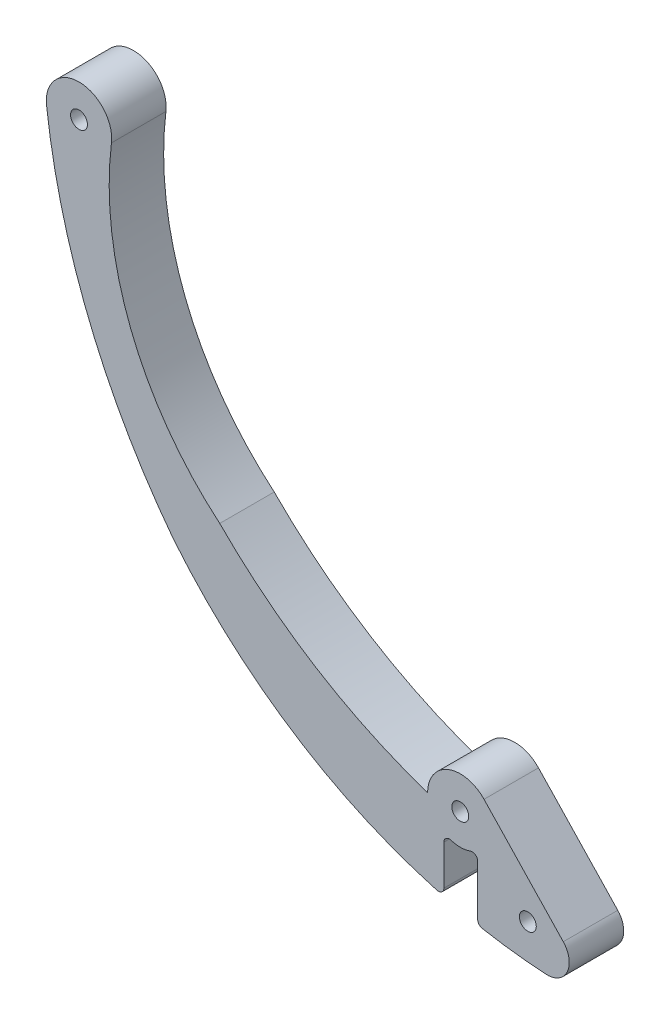
SolidWorks part; units mm, degrees
ref_plane "Plan de face" through (0, 0, 0) normal (0, 0, 1) x (1, 0, 0)
ref_plane "Plan de dessus" through (0, 0, 0) normal (0, 1, 0) x (1, 0, 0)
ref_plane "Plan de droite" through (0, 0, 0) normal (1, 0, 0) x (0, 0, -1)
sketch "Sketch2" plane through (0, 0, 0) normal (0, 0, 1) x (1, 0, 0)
  line L18 (2.9055, 2.7492) -> (-11.6417, 18.1238)
  line L19 (0, 0) -> (0, 14) construction
  line L20 (-16, 14) -> (0, 14) construction
  line L21 (-16, 14) -> (-16, 89) construction
  line L22 (-86, 89) -> (-16, 89) construction
  line L23 (0, 0) -> (0, 2.7054) construction
  line L24 (-3.6022, 2.7054) -> (0, 2.7054) construction
  arc A7 (-0.2326, -3.9932) -> (2.9055, 2.7492) centre (0, 0) ccw
  arc A8 (-11.6417, 18.1238) -> (-22, 14) centre (-16, 14) ccw
  arc A10 (-80.0437, 88.2774) -> (-91.9574, 88.286) centre (-86, 89) ccw
  arc A11 (-91.9574, 88.286) -> (-68.6302, 30.946) centre (24.4862, 102.2428) ccw
  arc A12 (-0.2326, -3.9932) -> (-68.6302, 30.946) centre (5.3171, 91.2888) cw
  circle A13 centre (-86, 89) radius 1.55
  circle A14 centre (-16, 14) radius 1.55
  arc A16 (-80.0437, 88.2774) -> (-60.1634, 37.7239) centre (-23.325, 81.3964) ccw
  arc A17 (-22, 14) -> (-60.1634, 37.7239) centre (8.7491, 106.0223) cw
  circle A18 centre (-3.6022, 2.7054) radius 1.55
  dimension "D5" = 16
  dimension "D6" = 75
  dimension "D7" = 70
  dimension "D8" = 3.1
  dimension "D1" = 8
  dimension "D2" = 12
  dimension "D3" = 12
  dimension "D9" = 3.1
  dimension "D10" = 3.1
  dimension "D4" = 14
  dimension "D11" = 2.7054
  dimension "D12" = 3.6022
extrude "Boss-Extrude1" add sketch "Sketch2" against normal blind 5 and the other way blind 5
sketch "Sketch3" plane through (0, 0, 5) normal (0, 0, 1) x (1, 0, 0)
  line L0 (-19.013, -1.0016) -> (-19.013, 9.1815)
  line L1 (-12.8052, -2.4184) -> (-12.8052, 9.3001)
  arc A0 (-68.6302, 30.946) -> (-0.2326, -3.9932) centre (5.3171, 91.2888) ccw construction
  arc A1 (-19.013, -1.0016) -> (-12.8052, -2.4184) centre (5.3171, 91.2888) ccw
  arc A2 (-19.013, 9.1815) -> (-12.8052, 9.3001) centre (-16, 14) ccw
  arc A3 (-11.6417, 18.1238) -> (-22, 14) centre (-16, 14) ccw construction
  point P9 (-17.555, 10.2866)
  point P10 (-11.7717, 9.8684)
  point P14 (-12.8052, 9.1815)
extrude "Cut-Extrude1" cut sketch "Sketch3" against normal up to surface (10 mm away) up to face at (-2.0522, 2.7054, -5)
fillet "Fillet1" radius 1 4 edges at (-19.013, 9.1815, 0) (-12.8052, 9.3001, 0) (-19.013, -1.0016, 0) (-12.8052, -2.4184, 0)
